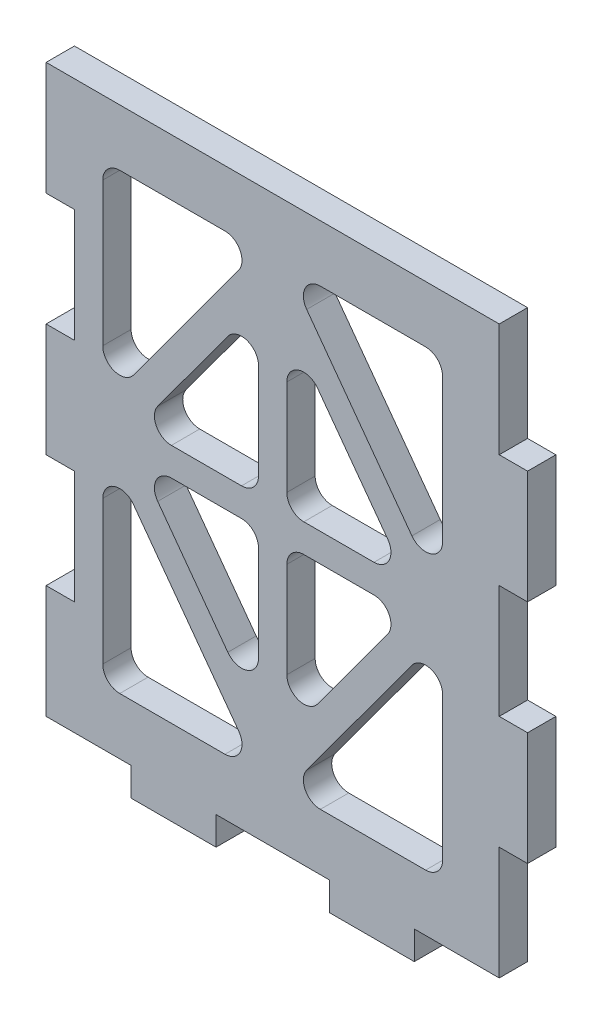
SolidWorks part; units mm, degrees
ref_plane "Front" through (0, 0, 0) normal (0, 0, 1) x (1, 0, 0)
ref_plane "Top" through (0, 0, 0) normal (0, 1, 0) x (1, 0, 0)
ref_plane "Right" through (0, 0, 0) normal (1, 0, 0) x (0, 0, -1)
sketch "Sketch1" plane through (0, 0, 0) normal (0, 0, 1) x (1, 0, 0)
  line L0 (-50.8, 38.1) -> (-50.8, 63.5)
  line L1 (-50.8, -63.5) -> (-31.75, -63.5)
  line L2 (-50.8, -63.5) -> (-50.8, -38.1)
  line L3 (-50.8, 63.5) -> (50.8, 63.5)
  line L4 (50.8, -63.5) -> (50.8, -38.1)
  line L5 (-50.8, -63.5) -> (50.8, 63.5) construction
  line L6 (-50.8, 63.5) -> (50.8, -63.5) construction
  line L7 (-50.8, 38.1) -> (-44.45, 38.1)
  line L8 (-50.8, -12.7) -> (-50.8, 12.7)
  line L9 (-50.8, 12.7) -> (-44.45, 12.7)
  line L10 (-44.45, 38.1) -> (-44.45, 12.7)
  line L11 (-50.8, -12.7) -> (-44.45, -12.7)
  line L12 (50.8, 38.1) -> (50.8, 63.5)
  line L13 (-50.8, -38.1) -> (-44.45, -38.1)
  line L14 (-44.45, -12.7) -> (-44.45, -38.1)
  line L15 (50.8, 38.1) -> (57.15, 38.1)
  line L16 (50.8, -12.7) -> (50.8, 12.7)
  line L17 (50.8, 12.7) -> (57.15, 12.7)
  line L18 (57.15, 38.1) -> (57.15, 12.7)
  line L19 (50.8, -12.7) -> (57.15, -12.7)
  line L20 (-12.7, -63.5) -> (12.7, -63.5)
  line L21 (50.8, -38.1) -> (57.15, -38.1)
  line L22 (57.15, -12.7) -> (57.15, -38.1)
  line L23 (31.75, -63.5) -> (50.8, -63.5)
  line L24 (-31.75, -63.5) -> (-31.75, -69.85)
  line L25 (-31.75, -69.85) -> (-12.7, -69.85)
  line L26 (-12.7, -63.5) -> (-12.7, -69.85)
  line L28 (12.7, -63.5) -> (12.7, -69.85)
  line L29 (12.7, -69.85) -> (31.75, -69.85)
  line L30 (31.75, -63.5) -> (31.75, -69.85)
  point P0 (0, 0)
  dimension "D1" = 127
  dimension "D2" = 101.6
  dimension "D3" = 6.35
  dimension "D4" = 25.4
  dimension "D5" = 25.4
  dimension "D6" = 25.4
  dimension "D7" = 6.35
  dimension "D8" = 19.05
  dimension "D9" = 19.05
  dimension "D10" = 19.05
extrude "BOXSIDE" add sketch "Sketch1" along normal blind 6.35 contours L3 L12 L15 L18 L17 L16 L19 L22 L21 L4 L23 L30 L29 L28 L20 L26 L25 L24 L1 L2 L13 L14 L11 L8 L9 L10 L7 L0
sketch "Sketch2" plane through (0, 0, 6.35) normal (0, 0, 1) x (1, 0, 0)
  line L0 (-38.1, 50.8) -> (-3.175, 50.8)
  line L1 (-3.175, 50.8) -> (-38.1, 3.175)
  line L2 (-38.1, 3.175) -> (-38.1, 50.8)
  line L3 (-3.175, 40.0621) -> (-3.175, 3.175)
  line L4 (-3.175, 3.175) -> (-30.2255, 3.175)
  line L5 (-30.2255, 3.175) -> (-3.175, 40.0621)
  line L6 (-50.8, 38.1) -> (-50.8, 63.5) construction
  line L7 (30.2255, 3.175) -> (3.175, 40.0621)
  line L8 (3.175, 3.175) -> (30.2255, 3.175)
  line L9 (3.175, 40.0621) -> (3.175, 3.175)
  line L10 (38.1, 3.175) -> (38.1, 50.8)
  line L11 (3.175, 50.8) -> (38.1, 3.175)
  line L12 (-50.8, 0) -> (50.8, 0) construction
  line L13 (-50.8, -12.7) -> (-50.8, 12.7) construction
  line L14 (50.8, -12.7) -> (50.8, 12.7) construction
  line L15 (0, 0) -> (0, 63.5) construction
  line L16 (-50.8, 63.5) -> (50.8, 63.5) construction
  line L17 (38.1, 50.8) -> (3.175, 50.8)
  line L18 (38.1, -50.8) -> (3.175, -50.8)
  line L19 (3.175, -50.8) -> (38.1, -3.175)
  line L20 (38.1, -3.175) -> (38.1, -50.8)
  line L21 (3.175, -40.0621) -> (3.175, -3.175)
  line L22 (3.175, -3.175) -> (30.2255, -3.175)
  line L23 (30.2255, -3.175) -> (3.175, -40.0621)
  line L24 (-30.2255, -3.175) -> (-3.175, -40.0621)
  line L25 (-3.175, -3.175) -> (-30.2255, -3.175)
  line L26 (-3.175, -40.0621) -> (-3.175, -3.175)
  line L27 (-38.1, -3.175) -> (-38.1, -50.8)
  line L28 (-3.175, -50.8) -> (-38.1, -3.175)
  line L29 (-38.1, -50.8) -> (-3.175, -50.8)
  dimension "D1" = 12.7
  dimension "D2" = 12.7
  dimension "D3" = 3.175
  dimension "D4" = 3.175
  dimension "D5" = 6.35
extrude "Cut-Extrude1" cut sketch "Sketch2" against normal through all
fillet "Fillet1" radius 3.81 24 edges at (-3.175, -50.8, 3.175) (-38.1, -3.175, 3.175) (-38.1, -50.8, 3.175) (3.175, -50.8, 3.175) (38.1, -50.8, 3.175) (38.1, -3.175, 3.175) (3.175, -40.0621, 3.175) (-3.175, -40.0621, 3.175) (-30.2255, -3.175, 3.175) (3.175, -3.175, 3.175) (30.2255, -3.175, 3.175) (-3.175, -3.175, 3.175) (-3.175, 3.175, 3.175) (-3.175, 40.0621, 3.175) (-30.2255, 3.175, 3.175) (-38.1, 3.175, 3.175) (30.2255, 3.175, 3.175) (3.175, 40.0621, 3.175) (3.175, 3.175, 3.175) (38.1, 3.175, 3.175) (38.1, 50.8, 3.175) (-3.175, 50.8, 3.175) (3.175, 50.8, 3.175) (-38.1, 50.8, 3.175)
